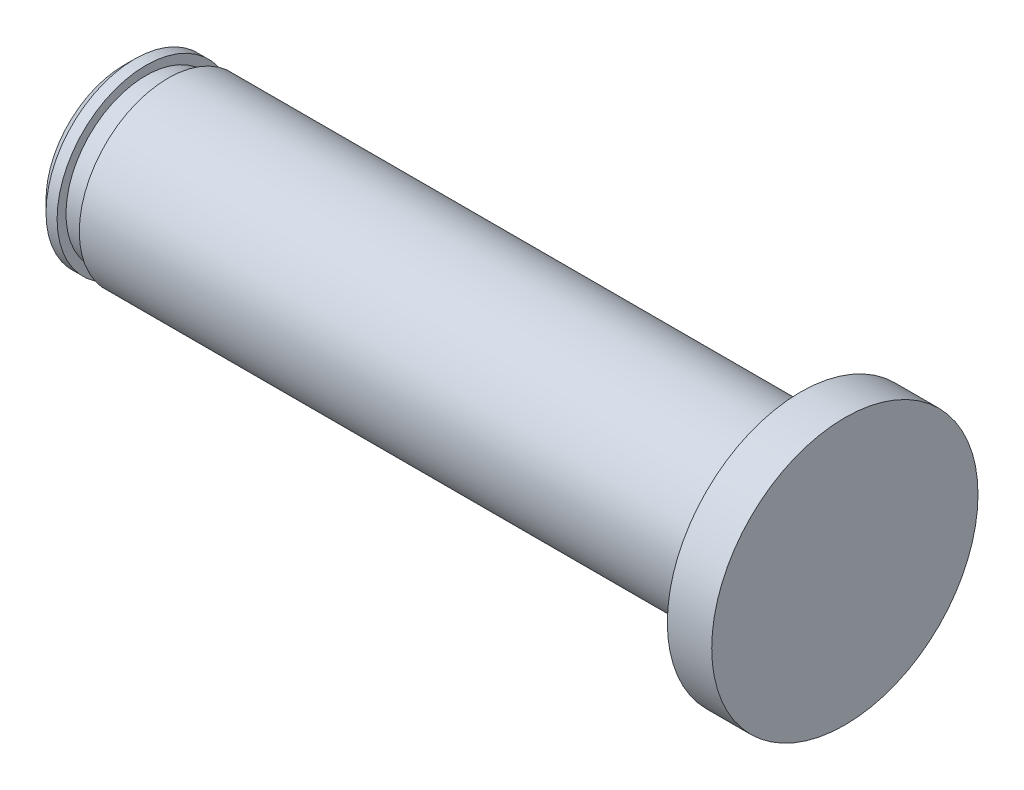
SolidWorks part; units mm, degrees
ref_plane "Спереди" through (0, 0, 0) normal (0, 0, 1) x (1, 0, 0)
ref_plane "Сверху" through (0, 0, 0) normal (0, 1, 0) x (1, 0, 0)
ref_plane "Справа" through (0, 0, 0) normal (1, 0, 0) x (0, 0, -1)
sketch "Эскиз1" plane through (0, 0, 0) normal (0, 0, 1) x (1, 0, 0)
  line L0 (0, 0) -> (-32.5, 0)
  line L1 (-32.5, 0) -> (-32.5, 4)
  line L2 (-32.5, 4) -> (-31.5, 4)
  line L3 (-31.5, 4) -> (-31.5, 3.6)
  line L4 (-31.5, 3.6) -> (-30.5, 3.6)
  line L5 (-30.5, 3.6) -> (-30.5, 4)
  line L6 (-30.5, 4) -> (-2, 4)
  line L7 (-2, 4) -> (-2, 6)
  line L8 (-2, 6) -> (0, 6)
  line L9 (0, 6) -> (0, 0)
  line L10 (-32.5, 0) -> (-24.8571, 0) construction
  line L11 (-32, 0) -> (-50032, 0) construction
  line L12 (-30.5, 4) -> (-30.5, -4) construction
  point P3 (0, 0)
  point P15 (0, 0)
  point P16 (0, 0)
  point P17 (0, 0)
  dimension "D1" = 8
  dimension "D3" = 2
  dimension "D4" = 2
  dimension "D5" = 1
  dimension "D6" = 1
  dimension "D7" = 7.2
revolve "Повернуть1" add sketch "Эскиз1" angle 360 about L10
chamfer "Фаска1" distance 0.5 angle 45 1 edges at (-32.5, -4, 0)
equation "\"Диаметр вала\" = 8  '!!!"
equation "\"Длина вала\" = 28"
equation "\"D1@Эскиз1\"=\"Диаметр вала\""
